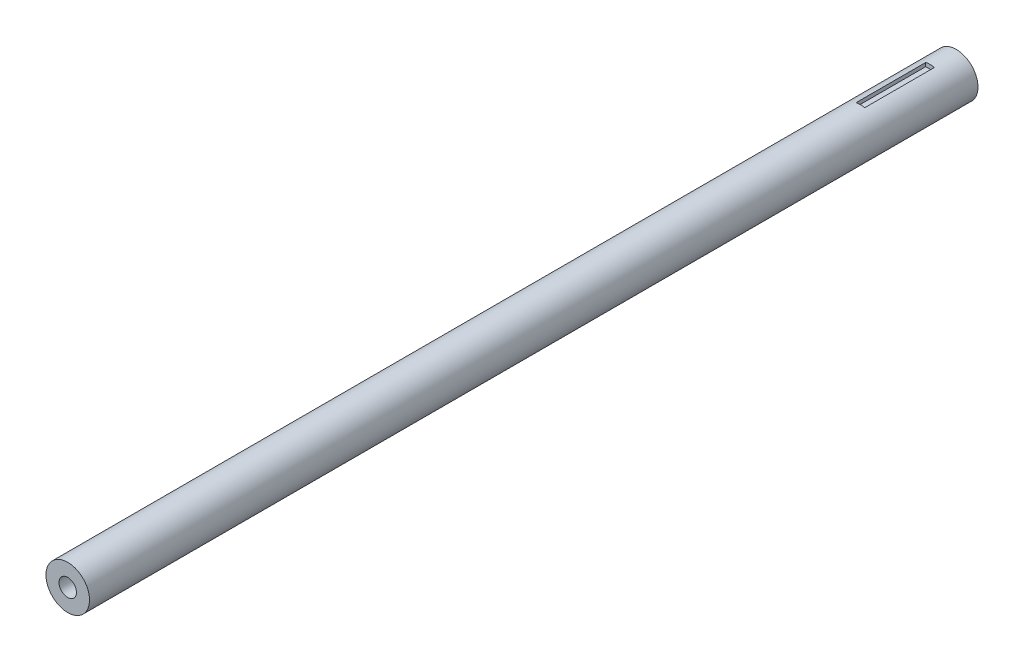
SolidWorks part; units mm, degrees
ref_plane "Front" through (0, 0, 0) normal (0, 0, 1) x (1, 0, 0)
ref_plane "Top" through (0, 0, 0) normal (0, 1, 0) x (1, 0, 0)
ref_plane "Right" through (0, 0, 0) normal (1, 0, 0) x (0, 0, -1)
sketch "Sketch1" plane through (0, 0, 0) normal (0, 0, 1) x (1, 0, 0)
  circle A0 centre (0, 0) radius 7.9375
  dimension "D1" = 15.875
extrude "Extrude1" add sketch "Sketch1" along normal blind 130.175 and the other way blind 193.675
ref_axis "Axis1" through (0, 0, 130.175) along (0, 0, -1)
sketch "Sketch2" plane through (0, 0, 130.175) normal (0, 0, 1) x (1, 0, 0)
  circle A0 centre (0, 0) radius 3.175
  dimension "D1" = 6.35
extrude "Cut-Extrude1" cut sketch "Sketch2" against normal blind 25.4
sketch "Sketch3" plane through (0, 0, 0) normal (1, 0, 0) x (0, 0, -1)
  line L0 (193.675, 7.9375) -> (-130.175, 7.9375) construction
  line L1 (193.675, -7.9375) -> (193.675, 7.9375) construction
  line L3 (158.75, 9.6139) -> (184.15, 9.6139)
  line L4 (158.75, 9.6139) -> (158.75, 6.4389)
  line L5 (158.75, 6.4389) -> (184.15, 6.4389)
  line L6 (184.15, 9.6139) -> (184.15, 6.4389)
  point P2 (184.15, 7.9375)
  dimension "D1" = 3.175
  dimension "D2" = 9.525
  dimension "D3" = 1.4986
  dimension "D4" = 25.4
extrude "Cut-Extrude2" cut sketch "Sketch3" against normal mid plane 3.175
